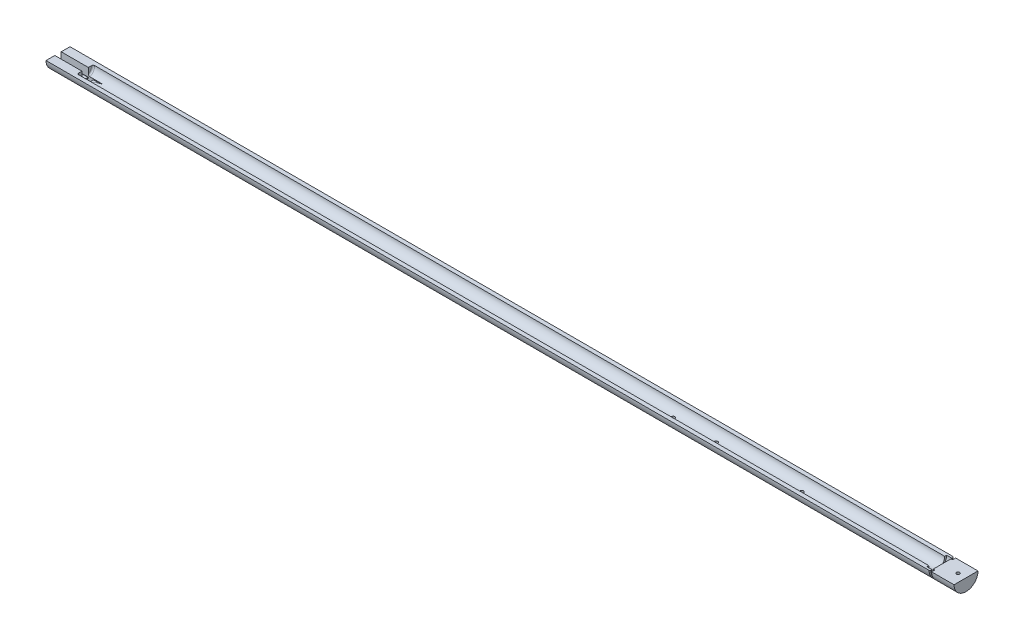
SolidWorks part; units mm, degrees
ref_plane "Front Plane" through (0, 0, 0) normal (0, 0, 1) x (1, 0, 0)
ref_plane "Top Plane" through (0, 0, 0) normal (0, 1, 0) x (1, 0, 0)
ref_plane "Right Plane" through (0, 0, 0) normal (1, 0, 0) x (0, 0, -1)
sketch "Sketch1" plane through (0, 0, 0) normal (0, 1, 0) x (1, 0, 0)
  line L1 (0, 0) -> (1803.4, 0)
  line L2 (0, 0) -> (0, 57.15)
  line L3 (0, 57.15) -> (1803.4, 57.15)
  line L4 (1803.4, 0) -> (1803.4, 57.15)
  dimension "blank_length" = 1803.4
  dimension "blank_width" = 57.15
extrude "wood block" add sketch "Sketch1" along normal blind 28.575
ref_plane "Plane1" through (0, 0, -28.575) normal (0, 0, 1) x (1, 0, 0)
sketch "Sketch2" plane through (0, 0, -28.575) normal (0, 0, 1) x (1, 0, 0)
  line L0 (1755.775, 28.575) -> (0, 28.575)
  line L2 (0, 12.7) -> (1755.775, 12.7)
  line L5 (0, 28.575) -> (0, 12.7)
  line L6 (0, 28.575) -> (0, 0) construction
  line L7 (1755.775, 28.575) -> (1755.775, 12.7)
  line L8 (0, 28.575) -> (1803.4, 28.575) construction
  dimension "bore_inner_radius" = 15.875
  dimension "finished_length" = 1755.775
revolve "Inner Bore" cut sketch "Sketch2" angle 360 about L0
sketch "Sketch12" plane through (0, 0, -28.575) normal (0, 0, 1) x (1, 0, 0)
  line L0 (0, 28.575) -> (1803.4, 28.575) construction
  line L1 (1745.234, 28.575) -> (1755.775, 28.575)
  line L2 (1745.234, 28.575) -> (1745.234, 8.89)
  line L3 (1745.234, 8.89) -> (1755.775, 8.89)
  line L4 (1755.775, 28.575) -> (1755.775, 8.89)
  line L5 (0, 28.575) -> (0, 0) construction
  dimension "flange_depth" = 10.541
  dimension "finished_length" = 1755.775
  dimension "flange_OD" = 19.685
revolve "Cut-Revolve1" cut sketch "Sketch12" angle 360 about L1
ref_axis "Axis1" through (0, 28.575, -28.575) along (1, 0, 0)
sketch "Sketch13" plane through (0, 0, 0) normal (-1, 0, 0) x (0, 0, 1)
  line L1 (-57.15, 0) -> (0, 0)
  line L2 (-57.15, 0) -> (-57.15, 28.575)
  line L3 (-57.15, 28.575) -> (0, 28.575)
  line L4 (0, 0) -> (0, 28.575)
  line L5 (-57.15, 0) -> (0, 28.575) construction
  line L6 (-57.15, 28.575) -> (0, 0) construction
  point P4 (-28.575, 14.2875)
extrude "Boss-Extrude1" add sketch "Sketch13" against normal blind 53.975
fillet "Fillet3" radius 3.175 1 edges at (53.975, 12.7, -28.575)
sketch "Sketch5" plane through (0, 0, -28.575) normal (0, 0, 1) x (1, 0, 0)
  line L0 (53.975, 28.575) -> (53.975, 12.1285)
  line L3 (53.975, 0) -> (64.135, 0)
  line L4 (64.135, 0) -> (64.135, 12.1285) construction
  line L6 (64.135, 28.575) -> (53.975, 28.575)
  line L13 (64.135, 12.1285) -> (97.4578, 0)
  line L14 (97.4578, 0) -> (64.135, 0)
  line L15 (64.135, 12.1285) -> (64.135, 28.575)
  line L16 (53.975, 12.1285) -> (48.9512, 0)
  line L17 (48.9512, 0) -> (53.975, 0)
  line L18 (53.975, 12.1285) -> (53.975, 0) construction
  line L29 (0, 0) -> (1803.4, 0) construction
  line L34 (0, 28.575) -> (0, 0) construction
  line L35 (0, 28.575) -> (1803.4, 28.575) construction
  line L36 (0, 0) -> (1803.4, 0) construction
  line L37 (64.135, 12.1285) -> (53.975, 12.1285) construction
  point P2 (53.975, 28.575)
  point P3 (53.975, 12.7)
  point P6 (1755.775, 28.575)
  point P11 (0, 28.575)
  point P12 (1803.4, 28.575)
  point P21 (53.975, 28.575)
  point P22 (1771.65, 28.575)
  point P23 (1755.775, 28.575)
  point P24 (53.975, 28.575)
  point P25 (38.1, 28.575)
  point P26 (53.975, 28.575)
  point P27 (1755.775, 28.575)
  point P28 (0, 28.575)
  point P29 (0, 0)
  point P30 (1803.4, 28.575)
  point P31 (1803.4, 0)
  point P32 (1803.4, 28.575)
  point P33 (1803.4, 0)
  point P34 (0, 28.575)
  point P35 (0, 0)
  point P36 (1803.4, 28.575)
  point P37 (0, 28.575)
  point P38 (1803.4, 0)
  point P39 (0, 0)
  point P40 (0, 0)
  point P41 (1803.4, 0)
  point P42 (1755.775, 28.575)
  point P43 (1755.775, 12.7)
  point P46 (1755.775, 28.575)
  point P47 (53.975, 28.575)
  point P48 (1771.65, 28.575)
  point P49 (1755.775, 28.575)
  point P50 (53.975, 28.575)
  point P51 (38.1, 28.575)
  point P52 (53.975, 28.575)
  point P53 (1755.775, 28.575)
  dimension "fipple_gap" = 10.16
  dimension "fipple_ramp" = 20
  dimension "flue_depth" = 12.1285
  dimension "gap_beginning" = 53.975
  dimension "flue_dam" = 22.5
extrude "fipple" cut sketch "Sketch5" against normal mid plane 12.7
sketch "Sketch3" plane through (0, 28.575, 0) normal (0, 1, 0) x (1, 0, 0)
  line L122 (64.135, 34.925) -> (64.135, 22.225) construction
  line L123 (1476.629, 28.575) -> (1306.449, 28.575) construction
  line L124 (1306.449, 28.575) -> (1221.359, 28.575) construction
  line L125 (1221.359, 28.575) -> (64.135, 28.575) construction
  circle A0 centre (1476.629, 28.575) radius 3.81
  circle A1 centre (1306.449, 28.575) radius 3.81
  circle A2 centre (1221.359, 28.575) radius 3.81
  point P2 (-6.496, 28.575)
  point P3 (6.496, 28.575)
  point P10 (53.975, 22.225)
  point P11 (74.081, 22.225)
  point P12 (53.975, 34.925)
  point P13 (64.135, 34.925)
  point P14 (64.135, 34.925)
  point P15 (64.135, 22.225)
  point P16 (53.975, 22.225)
  point P17 (64.135, 22.225)
  point P18 (1724.025, 44.45)
  point P19 (53.975, 44.45)
  point P20 (1724.025, 28.575)
  point P21 (1724.025, 12.7)
  point P22 (1724.025, 44.45)
  point P23 (53.975, 28.575)
  point P24 (53.975, 44.45)
  point P25 (53.975, 12.7)
  point P26 (53.975, 12.7)
  point P27 (1724.025, 12.7)
  point P28 (1803.4, 4.7625)
  point P29 (1803.4, 52.3875)
  point P30 (0, 52.3875)
  point P31 (0, 4.7625)
  point P32 (53.975, 12.7)
  point P33 (53.975, 22.225)
  point P34 (53.975, 22.225)
  point P35 (53.975, 34.925)
  point P36 (53.975, 34.925)
  point P37 (53.975, 44.45)
  point P38 (1724.025, 12.7)
  point P39 (1724.025, 44.45)
  point P40 (64.135, 34.925)
  point P41 (64.135, 22.225)
  point P42 (74.081, 34.925)
  point P43 (64.135, 34.925)
  point P44 (74.081, 22.225)
  point P45 (64.135, 22.225)
  point P46 (1803.4, 4.7625)
  point P47 (0, 4.7625)
  point P48 (0, 52.3875)
  point P49 (1803.4, 52.3875)
  point P50 (53.975, 34.925)
  point P51 (74.081, 34.925)
  point P52 (74.081, 22.225)
  point P53 (74.081, 34.925)
  point P54 (-54.3985, 28.575)
  point P55 (76.4501, 28.575)
  point P56 (11.0258, 4.7625)
  point P57 (11.0258, 52.3875)
  point P58 (11.0258, 28.575)
  point P59 (53.975, 22.225)
  point P60 (53.975, 34.925)
  point P61 (1803.4, 4.7625)
  point P62 (1803.4, 52.3875)
  point P63 (0, 52.3875)
  point P64 (0, 4.7625)
  point P65 (0, 0)
  point P66 (1803.4, 0)
  point P67 (0, 0)
  point P68 (0, 57.15)
  point P69 (0, 57.15)
  point P70 (1803.4, 57.15)
  point P71 (1803.4, 0)
  point P72 (1803.4, 57.15)
  point P73 (1739.9, 28.575)
  point P74 (38.1, 28.575)
  point P75 (0, 28.575)
  point P76 (1803.4, 28.575)
  point P77 (53.975, 28.575)
  point P78 (1724.025, 28.575)
  point P79 (1803.4, 28.575)
  point P80 (0, 28.575)
  point P81 (53.975, 28.575)
  point P82 (64.135, 28.575)
  point P83 (64.135, 28.575)
  point P84 (53.975, 28.575)
  point P85 (0, 28.575)
  point P86 (1803.4, 28.575)
  point P87 (0, 28.575)
  point P88 (159.6887, 28.575)
  point P89 (0, 28.575)
  point P90 (159.6887, 28.575)
  point P91 (64.135, 28.575)
  point P92 (89.535, 28.575)
  point P93 (89.535, 28.575)
  point P94 (64.135, 28.575)
  point P95 (0, 57.15)
  point P96 (0, 0)
  point P97 (-13.0969, 0)
  point P98 (13.0969, 0)
  point P99 (0, -13.0969)
  point P100 (0, 13.0969)
  point P101 (53.975, 22.225)
  point P102 (74.081, 22.225)
  point P103 (53.975, 34.925)
  point P104 (64.135, 34.925)
  point P105 (64.135, 34.925)
  point P106 (64.135, 22.225)
  point P107 (53.975, 22.225)
  point P108 (64.135, 22.225)
  point P109 (1724.025, 44.45)
  point P110 (53.975, 44.45)
  point P111 (1724.025, 28.575)
  point P112 (1724.025, 12.7)
  point P113 (1724.025, 44.45)
  point P114 (53.975, 28.575)
  point P115 (53.975, 44.45)
  point P116 (53.975, 12.7)
  point P117 (53.975, 12.7)
  point P118 (1724.025, 12.7)
  point P119 (1803.4, 4.7625)
  point P120 (1803.4, 52.3875)
  point P121 (0, 52.3875)
  point P122 (0, 4.7625)
  point P123 (53.975, 12.7)
  point P124 (53.975, 22.225)
  point P125 (53.975, 22.225)
  point P126 (53.975, 34.925)
  point P127 (53.975, 34.925)
  point P128 (53.975, 44.45)
  point P129 (1724.025, 12.7)
  point P130 (1724.025, 44.45)
  point P131 (64.135, 34.925)
  point P132 (64.135, 22.225)
  point P133 (74.081, 34.925)
  point P134 (64.135, 34.925)
  point P135 (74.081, 22.225)
  point P136 (64.135, 22.225)
  point P137 (1803.4, 4.7625)
  point P138 (0, 4.7625)
  point P139 (0, 52.3875)
  point P140 (1803.4, 52.3875)
  point P141 (53.975, 34.925)
  point P142 (74.081, 34.925)
  point P143 (74.081, 22.225)
  point P144 (74.081, 34.925)
  point P145 (-54.3985, 28.575)
  point P146 (76.4501, 28.575)
  point P147 (11.0258, 4.7625)
  point P148 (11.0258, 52.3875)
  point P149 (11.0258, 28.575)
  point P150 (53.975, 22.225)
  point P151 (53.975, 34.925)
  point P152 (1803.4, 4.7625)
  point P153 (1803.4, 52.3875)
  point P154 (0, 52.3875)
  point P155 (0, 4.7625)
  point P156 (0, 0)
  point P157 (1803.4, 0)
  point P158 (0, 0)
  point P159 (0, 57.15)
  point P160 (0, 57.15)
  point P161 (1803.4, 57.15)
  point P162 (1803.4, 0)
  point P163 (1803.4, 57.15)
  point P164 (1739.9, 28.575)
  point P165 (38.1, 28.575)
  point P166 (0, 28.575)
  point P167 (1803.4, 28.575)
  point P168 (53.975, 28.575)
  point P169 (1724.025, 28.575)
  point P170 (1803.4, 28.575)
  point P171 (0, 28.575)
  point P172 (53.975, 28.575)
  point P173 (64.135, 28.575)
  point P174 (64.135, 28.575)
  point P175 (53.975, 28.575)
  point P176 (0, 28.575)
  point P177 (1803.4, 28.575)
  point P178 (0, 28.575)
  point P179 (159.6887, 28.575)
  point P180 (0, 28.575)
  point P181 (159.6887, 28.575)
  point P182 (64.135, 28.575)
  point P183 (89.535, 28.575)
  point P184 (89.535, 28.575)
  point P185 (64.135, 28.575)
  point P186 (0, 57.15)
  point P187 (0, 0)
  point P188 (-13.0969, 0)
  point P189 (13.0969, 0)
  point P190 (0, -13.0969)
  point P191 (0, 13.0969)
  point P192 (-6.496, 28.575)
  point P193 (6.496, 28.575)
  point P194 (53.975, 22.225)
  point P195 (74.081, 22.225)
  point P196 (53.975, 34.925)
  point P197 (64.135, 34.925)
  point P198 (64.135, 34.925)
  point P199 (64.135, 22.225)
  point P200 (53.975, 22.225)
  point P201 (64.135, 22.225)
  point P202 (1724.025, 44.45)
  point P203 (53.975, 44.45)
  point P204 (1724.025, 28.575)
  point P205 (1724.025, 12.7)
  point P206 (1724.025, 44.45)
  point P207 (53.975, 28.575)
  point P208 (53.975, 44.45)
  point P209 (53.975, 12.7)
  point P210 (53.975, 12.7)
  point P211 (1724.025, 12.7)
  point P212 (1803.4, 4.7625)
  point P213 (1803.4, 52.3875)
  point P214 (0, 52.3875)
  point P215 (0, 4.7625)
  point P216 (53.975, 12.7)
  point P217 (53.975, 22.225)
  point P218 (53.975, 22.225)
  point P219 (53.975, 34.925)
  point P220 (53.975, 34.925)
  point P221 (53.975, 44.45)
  point P222 (1724.025, 12.7)
  point P223 (1724.025, 44.45)
  point P224 (64.135, 34.925)
  point P225 (64.135, 22.225)
  point P226 (74.081, 34.925)
  point P227 (64.135, 34.925)
  point P228 (74.081, 22.225)
  point P229 (64.135, 22.225)
  point P230 (1803.4, 4.7625)
  point P231 (0, 4.7625)
  point P232 (0, 52.3875)
  point P233 (1803.4, 52.3875)
  point P234 (53.975, 34.925)
  point P235 (74.081, 34.925)
  point P236 (74.081, 22.225)
  point P237 (74.081, 34.925)
  point P238 (-54.3985, 28.575)
  point P239 (76.4501, 28.575)
  point P240 (11.0258, 4.7625)
  point P241 (11.0258, 52.3875)
  point P242 (11.0258, 28.575)
  point P243 (53.975, 22.225)
  point P244 (53.975, 34.925)
  point P245 (1803.4, 4.7625)
  point P246 (1803.4, 52.3875)
  point P247 (0, 52.3875)
  point P248 (0, 4.7625)
  point P249 (0, 0)
  point P250 (1803.4, 0)
  point P251 (0, 0)
  point P252 (0, 57.15)
  point P253 (0, 57.15)
  point P254 (1803.4, 57.15)
  point P255 (1803.4, 0)
  point P256 (1803.4, 57.15)
  point P257 (1739.9, 28.575)
  point P258 (38.1, 28.575)
  point P259 (0, 28.575)
  point P260 (1803.4, 28.575)
  point P261 (53.975, 28.575)
  point P262 (1724.025, 28.575)
  point P263 (1803.4, 28.575)
  point P264 (0, 28.575)
  point P265 (53.975, 28.575)
  point P266 (64.135, 28.575)
  point P267 (64.135, 28.575)
  point P268 (53.975, 28.575)
  point P269 (0, 28.575)
  point P270 (1803.4, 28.575)
  point P271 (0, 28.575)
  point P272 (159.6887, 28.575)
  point P273 (0, 28.575)
  point P274 (159.6887, 28.575)
  point P275 (64.135, 28.575)
  point P276 (89.535, 28.575)
  point P277 (89.535, 28.575)
  point P278 (64.135, 28.575)
  point P279 (0, 57.15)
  point P280 (0, 0)
  point P281 (-13.0969, 0)
  point P282 (13.0969, 0)
  point P283 (0, -13.0969)
  point P284 (0, 13.0969)
  point P285 (-6.496, 28.575)
  point P286 (6.496, 28.575)
  dimension "hole3_diameter" = 7.62
  dimension "hole2_diameter" = 7.62
  dimension "hole1_diameter" = 7.62
  dimension "fipple_to_hole1" = 1157.224
  dimension "fipple_to_hole2" = 1242.314
  dimension "fipple_to_hole3" = 1412.494
extrude "finger holes" cut sketch "Sketch3" against normal blind 25.4
sketch "Sketch9" plane through (0, 0, -28.575) normal (0, 0, 1) x (1, 0, 0)
  line L0 (64.135, 12.3825) -> (84.3737, 14.1532)
  line L1 (64.135, 12.1285) -> (64.135, 14.0253) construction
  line L2 (84.3737, 14.1532) -> (64.135, 16.8013)
  line L3 (64.135, 16.8013) -> (64.135, 12.3825)
  line L4 (1803.4, 28.575) -> (0, 28.575) construction
  dimension "fipple_height" = 0.254
  dimension "fipple_ramp_in" = 5
extrude "fipple inside chamfer" cut sketch "Sketch9" against normal up to vertex (6.35 mm away) and the other way up to vertex (6.35 mm away) up to point (57.15, 14.0253, -34.925) other way up to point (57.15, 14.0253, -22.225)
sketch "Sketch8" plane through (0, 0, 0) normal (-1, 0, 0) x (0, 0, 1)
  line L0 (-28.575, 28.575) -> (-28.575, 20.035) construction
  line L2 (-34.925, 17.5765) -> (-34.925, 12.1285) construction
  line L3 (-22.225, 28.575) -> (-34.925, 28.575)
  line L4 (-22.225, 28.575) -> (-22.225, 11.4951)
  line L5 (-22.225, 11.4951) -> (-34.925, 11.4951)
  line L6 (-34.925, 28.575) -> (-34.925, 11.4951)
  line L7 (-22.225, 28.575) -> (-34.925, 11.4951) construction
  line L8 (-22.225, 11.4951) -> (-34.925, 28.575) construction
  line L9 (-8.89, 28.575) -> (-48.26, 28.575) construction
  line L10 (-22.225, 12.3333) -> (-34.925, 12.3333) construction
  dimension "flue_depth" = 0.8382
extrude "flue" cut sketch "Sketch8" against normal up to next
fillet "Fillet1" radius 0.381 8 edges at (73.5238, 13.2039, -22.225) (73.5238, 13.2039, -34.925) (26.8563, 11.4951, -34.925) (26.8563, 11.4951, -22.225) (51.3319, 5.7475, -34.925) (51.3319, 5.7475, -22.225) (80.7964, 6.0643, -22.225) (80.7964, 6.0643, -34.925)
sketch "Sketch10" plane through (0, 28.575, 0) normal (0, 1, 0) x (1, 0, 0)
  line L0 (1803.4, 28.575) -> (1787.525, 28.575) construction
  line L1 (1803.4, 0) -> (1803.4, 57.15) construction
  circle A2 centre (1787.525, 28.575) radius 3.175
  dimension "dowel_pin_diameter" = 6.35
  dimension "dowel_pin_location" = 15.875
extrude "dowel pin hole" cut sketch "Sketch10" against normal blind 15.24
chamfer "Chamfer1" distance 16.7386 angle 45 2 edges at (901.7, 0, 0) (901.7, 0, -57.15)
sketch "Sketch6" plane through (0, 0, 0) normal (-1, 0, 0) x (0, 0, 1)
  line L0 (-8.89, 28.575) -> (-48.26, 28.575) construction
  circle A0 centre (-28.575, 28.575) radius 23.8125
  dimension "outer_diameter" = 47.625
extrude "outside diameter" cut sketch "Sketch6" against normal through all flip side to cut
sketch "Sketch11" plane through (0, 28.575, 0) normal (0, 1, 0) x (1, 0, 0)
  line L0 (1755.775, 4.7625) -> (1755.775, 12.7) construction
  line L1 (1803.4, 4.7625) -> (0, 4.7625) construction
  line L2 (1803.4, 4.7625) -> (1803.4, 52.3875) construction
  line L3 (1755.775, 4.7625) -> (1758.95, 4.7625)
  line L4 (1755.775, 4.7625) -> (1755.775, 11.1125)
  line L5 (1755.775, 11.1125) -> (1758.95, 11.1125)
  line L6 (1758.95, 4.7625) -> (1758.95, 11.1125)
  line L7 (0, 52.3875) -> (0, 34.925) construction
  dimension "groove_width" = 3.175
  dimension "groove_depth" = 6.35
  dimension "groove_location" = 47.625
  dimension "finished_length" = 1755.775
revolve "end length locator" cut sketch "Sketch11" angle 360 about axis through (0, 28.575, -28.575) along (1, 0, 0)
chamfer "chamfer at foot" distance 1.905 angle 45 1 edges at (1755.775, 4.7625, -28.575)
equation "\"g_body_OD\"= 47.625mm"
equation "\"g_body_ID\"= 31.75mm"
equation "\"g_body_L_finished\"= 1755.775mm"
equation "\"g_body_L_blank\"= 1803.4mm"
equation "\"g_body_blank_W\"= 57.15mm"
equation "\"g_dowel_OD\"= 6.35mm"
equation "\"g_thru_passage_OD\"= 12.7mm"
equation "\"g_glue_glap\"= 0.0762mm"
equation "\"c_dowel_clearance\"= 0mm"
equation "\"thickness@wood block\"= \"g_body_blank_W\" / 2"
equation "\"blank_length@Sketch1\"= \"g_body_L_blank\""
equation "\"blank_width@Sketch1\"= \"g_body_blank_W\""
equation "\"bore_inner_radius@Sketch2\"= \"g_body_ID\" / 2"
equation "\"outer_diameter@Sketch6\"= \"g_body_OD\""
equation "\"finished_length@Sketch11\"= \"g_body_L_finished\""
equation "\"dowel_pin_diameter@Sketch10\"= \"g_dowel_OD\" + \"c_dowel_clearance\""
